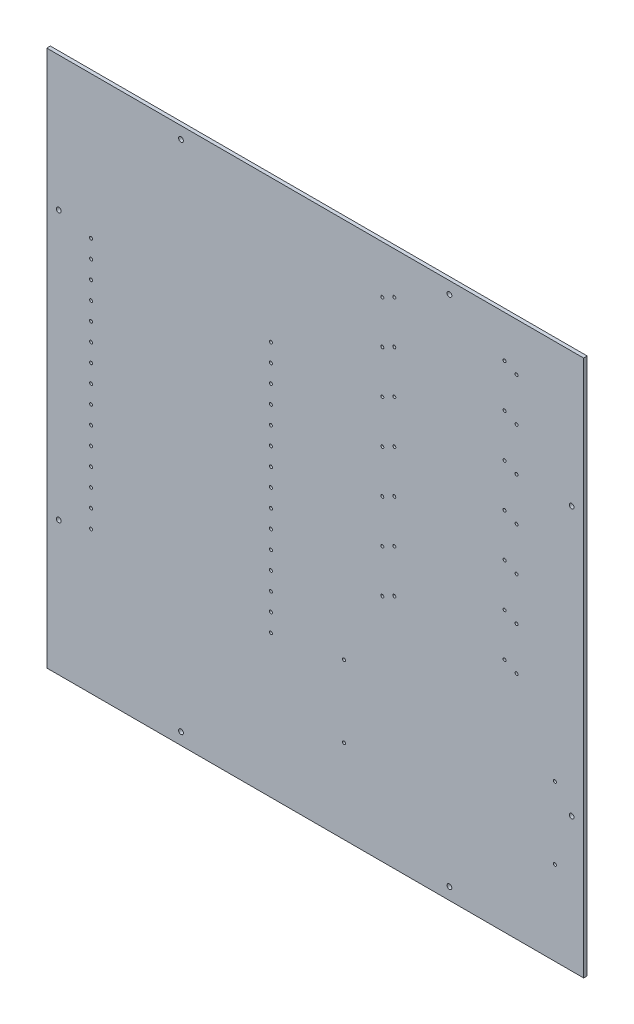
SolidWorks part; units mm, degrees
material "6061-T6 (SS)"
ref_plane "Piano frontale" through (0, 0, 0) normal (0, 0, 1) x (1, 0, 0)
ref_plane "Piano superiore" through (0, 0, 0) normal (0, 1, 0) x (1, 0, 0)
ref_plane "Piano destro" through (0, 0, 0) normal (1, 0, 0) x (0, 0, -1)
sketch "Schizzo1" plane through (0, 0, 0) normal (0, 0, 1) x (1, 0, 0)
  line L0 (10, 448) -> (10, -28.2593) construction
  line L1 (0, 0) -> (448, 0)
  line L2 (0, 0) -> (0, 448)
  line L3 (0, 448) -> (448, 448)
  line L4 (448, 0) -> (448, 448)
  line L5 (0, 224) -> (448, 224) construction
  line L6 (224, 448) -> (224, 0) construction
  line L7 (438, 448) -> (438, -28.2593) construction
  line L8 (0, 438) -> (525.0128, 438) construction
  line L9 (0, 10) -> (525.0128, 10) construction
  line L10 (0, 448) -> (0, 224) construction
  line L11 (0, 448) -> (0, 224) construction
  line L15 (0, 336) -> (224, 336) construction
  line L25 (112, 448) -> (112, 224) construction
  line L38 (36.9588, 287.1268) -> (36.9588, 448) construction
  line L39 (290, 454.3859) -> (290, -79.8136) construction
  line L40 (382, 454.3859) -> (382, -79.8136) construction
  line L41 (280, 457.4164) -> (280, -41.798) construction
  line L42 (392, 457.4164) -> (392, -41.798) construction
  line L43 (204.2813, 100) -> (482.2381, 100) construction
  line L44 (183.4892, 70) -> (499.6284, 70) construction
  line L45 (248, -38.4576) -> (248, 170.1585) construction
  line L46 (183.4892, 130) -> (499.6284, 130) construction
  line L47 (424, -38.4576) -> (424, 170.1585) construction
  line L58 (336, 27.7675) -> (336, 161.4481) construction
  line L65 (224, 224) -> (448, 224) construction
  circle A0 centre (10, 336) radius 2
  circle A1 centre (336, 438) radius 2
  circle A2 centre (438, 336) radius 2
  circle A3 centre (438, 112) radius 2
  circle A4 centre (336, 10) radius 2
  circle A5 centre (112, 10) radius 2
  circle A6 centre (10, 112) radius 2
  circle A7 centre (36.9588, 224) radius 1.25
  circle A8 centre (112, 438) radius 2
  circle A9 centre (36.9588, 239) radius 1.25
  circle A10 centre (36.9588, 254) radius 1.25
  circle A11 centre (36.9588, 269) radius 1.25
  circle A12 centre (36.9588, 284) radius 1.25
  circle A13 centre (36.9588, 299) radius 1.25
  circle A14 centre (36.9588, 314) radius 1.25
  circle A15 centre (36.9588, 329) radius 1.25
  circle A16 centre (248, 70) radius 1.25
  circle A17 centre (248, 130) radius 1.25
  circle A18 centre (424, 130) radius 1.25
  circle A19 centre (424, 70) radius 1.25
  circle A20 centre (290, 413) radius 1.25
  circle A21 centre (280, 408) radius 1.25
  circle A22 centre (392, 408) radius 1.25
  circle A23 centre (382, 413) radius 1.25
  circle A24 centre (290, 377) radius 1.25
  circle A25 centre (280, 372) radius 1.25
  circle A26 centre (392, 372) radius 1.25
  circle A27 centre (382, 377) radius 1.25
  circle A28 centre (290, 341) radius 1.25
  circle A29 centre (280, 336) radius 1.25
  circle A30 centre (392, 336) radius 1.25
  circle A31 centre (382, 341) radius 1.25
  circle A32 centre (290, 305) radius 1.25
  circle A33 centre (280, 300) radius 1.25
  circle A34 centre (392, 300) radius 1.25
  circle A35 centre (382, 305) radius 1.25
  circle A36 centre (290, 269) radius 1.25
  circle A37 centre (280, 264) radius 1.25
  circle A38 centre (392, 264) radius 1.25
  circle A39 centre (382, 269) radius 1.25
  circle A40 centre (290, 233) radius 1.25
  circle A41 centre (280, 228) radius 1.25
  circle A42 centre (392, 228) radius 1.25
  circle A43 centre (382, 233) radius 1.25
  circle A44 centre (290, 197) radius 1.25
  circle A45 centre (280, 192) radius 1.25
  circle A46 centre (392, 192) radius 1.25
  circle A47 centre (382, 197) radius 1.25
  circle A48 centre (36.9588, 119) radius 1.25
  circle A49 centre (36.9588, 134) radius 1.25
  circle A50 centre (36.9588, 149) radius 1.25
  circle A51 centre (36.9588, 164) radius 1.25
  circle A52 centre (36.9588, 179) radius 1.25
  circle A53 centre (36.9588, 194) radius 1.25
  circle A54 centre (36.9588, 209) radius 1.25
  circle A55 centre (187.0412, 209) radius 1.25
  circle A56 centre (187.0412, 194) radius 1.25
  circle A57 centre (187.0412, 179) radius 1.25
  circle A58 centre (187.0412, 164) radius 1.25
  circle A59 centre (187.0412, 149) radius 1.25
  circle A60 centre (187.0412, 134) radius 1.25
  circle A61 centre (187.0412, 119) radius 1.25
  circle A62 centre (187.0412, 329) radius 1.25
  circle A63 centre (187.0412, 314) radius 1.25
  circle A64 centre (187.0412, 299) radius 1.25
  circle A65 centre (187.0412, 284) radius 1.25
  circle A66 centre (187.0412, 269) radius 1.25
  circle A67 centre (187.0412, 254) radius 1.25
  circle A68 centre (187.0412, 239) radius 1.25
  circle A69 centre (187.0412, 224) radius 1.25
  point P33 (36.9588, 224)
  point P49 (112, 438)
  point P82 (253.9707, 256)
  point P89 (253.9707, 224)
  point P96 (253.9707, 192)
  point P103 (253.9707, 384)
  point P110 (253.9707, 352)
  point P117 (253.9707, 320)
  point P141 (253.9707, 288)
  point P148 (253.9707, 160)
  point P155 (253.9707, 128)
  point P162 (253.9707, 96)
  point P169 (253.9707, 64)
  point P179 (280.1758, 232.4048)
  point P193 (280.1085, 282.4047)
  point P207 (280.0413, 332.4047)
  dimension "D5" = 30
  dimension "D14" = 100
  dimension "D18" = 7
  dimension "D16" = 2.5
  dimension "D17" = 2.5
  dimension "D9" = 4
  dimension "D10" = 2.5
  dimension "D1" = 448
  dimension "D2" = 448
  dimension "D3" = 10
  dimension "D4" = 10
  dimension "D6" = 25
  dimension "D7" = 112
  dimension "D8" = 112
  dimension "D11" = 46
  dimension "D12" = 56
  dimension "D13" = 30
  dimension "D15" = 88
  dimension "D19" = 8
extrude "Estrusione-Estrusione1" add sketch "Schizzo1" against normal blind 3
